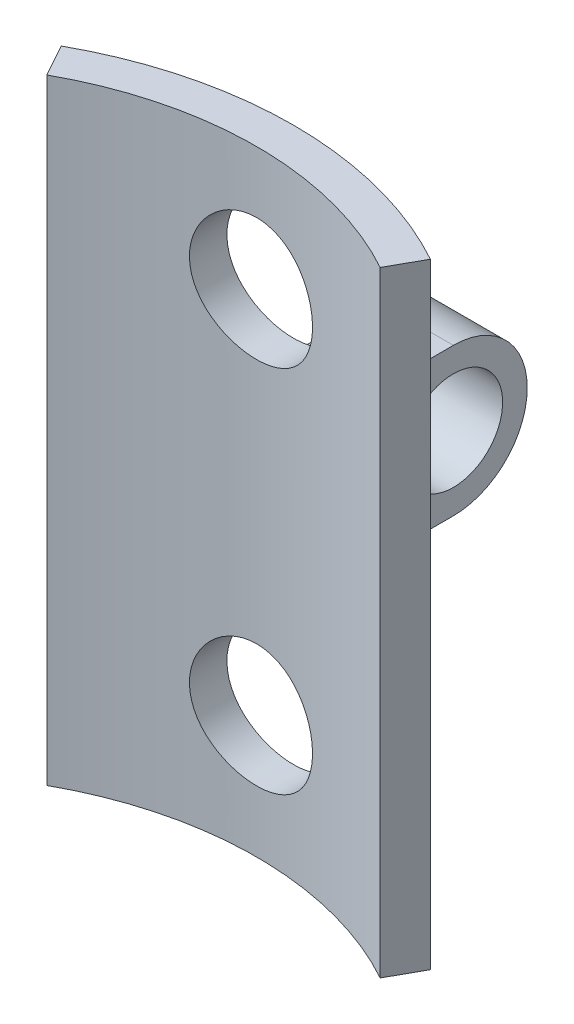
SolidWorks part; units mm, degrees
material "1060 Alloy"
ref_plane "Front Plane" through (0, 0, 0) normal (0, 0, 1) x (1, 0, 0)
ref_plane "Top Plane" through (0, 0, 0) normal (0, 1, 0) x (1, 0, 0)
ref_plane "Right Plane" through (0, 0, 0) normal (1, 0, 0) x (0, 0, -1)
sketch "Sketch2" plane through (0, 0, 0) normal (0, 1, 0) x (1, 0, 0)
  circle A0 centre (0, 0) radius 14
  circle A1 centre (0, 0) radius 15.5
  dimension "D1" = 28
  dimension "D2" = 1.5
extrude "Boss-Extrude1" add sketch "Sketch2" along normal blind 25
sketch "Sketch3" plane through (0, 25, 0) normal (0, 1, 0) x (1, 0, 0)
  line L0 (0, 0) -> (7.5, 13.5647)
  line L1 (0, 0) -> (-7.5, 13.5647)
  line L2 (7.5, 13.5647) -> (-7.5, 13.5647) construction
  circle A0 centre (0, 0) radius 15.5 construction
  arc A1 (7.5, 13.5647) -> (-7.5, 13.5647) centre (0, 0) ccw
  point P6 (0, 15.5)
  dimension "D1" = 15
extrude "Cut-Extrude1" cut sketch "Sketch3" against normal through all flip side to cut
sketch "Sketch5" plane through (0, 0, 0) normal (0, 0, 1) x (1, 0, 0)
  line L2 (0, 20) -> (0, 25) construction
  line L3 (6.7742, 25) -> (-6.7742, 25) construction
  line L4 (0, 25) -> (0, 20) construction
  line L5 (0, 5) -> (0, 0) construction
  circle A0 centre (0, 20) radius 2.5
  circle A1 centre (0, 5) radius 2.5
  dimension "D1" = 5
  dimension "D2" = 15
extrude "Cut-Extrude2" cut sketch "Sketch5" against normal through all
ref_plane "Plane1" through (0, 12.5, 0) normal (0, 1, 0) x (1, 0, 0)
sketch "Sketch6" plane through (0, 7.5, 0) normal (-1, 0, 0) x (0, 1, 0)
  line L0 (2, 20.5) -> (2, 15.25)
  line L1 (8, 20.5) -> (8, 15.25)
  line L2 (10, 15.5) -> (0, 15.5) construction
  line L3 (17.5, 12.252) -> (-7.5, 12.252) construction
  line L4 (2, 15.25) -> (8, 15.25)
  line L5 (10, 15.5) -> (0, 15.5) construction
  circle A0 centre (5, 20.5) radius 2
  arc A1 (8, 20.5) -> (2, 20.5) centre (5, 20.5) ccw
  point P10 (5, 12.252)
  dimension "D1" = 4
  dimension "D2" = 1
  dimension "D4" = 5
  dimension "D3" = 0.25
extrude "Boss-Extrude2" add sketch "Sketch6" along normal blind 1.5 and the other way blind 1.5
fillet "Fillet1" radius 1 2 edges at (1.5, 12.5, -15.4272) (-1.5, 12.5, -15.4272)
equation "\"keelOutDiameter\"= 1in"
equation "\"poleOutDiameter\"= 28mm"
equation "\"poleLength\"=650mm"
equation "\"propellerTubeOutDiameter\"= 28mm"
equation "\"propellerDiameter\"= 700mm"
equation "\"D1@Sketch2\"=\"propellerTubeOutDiameter\""
